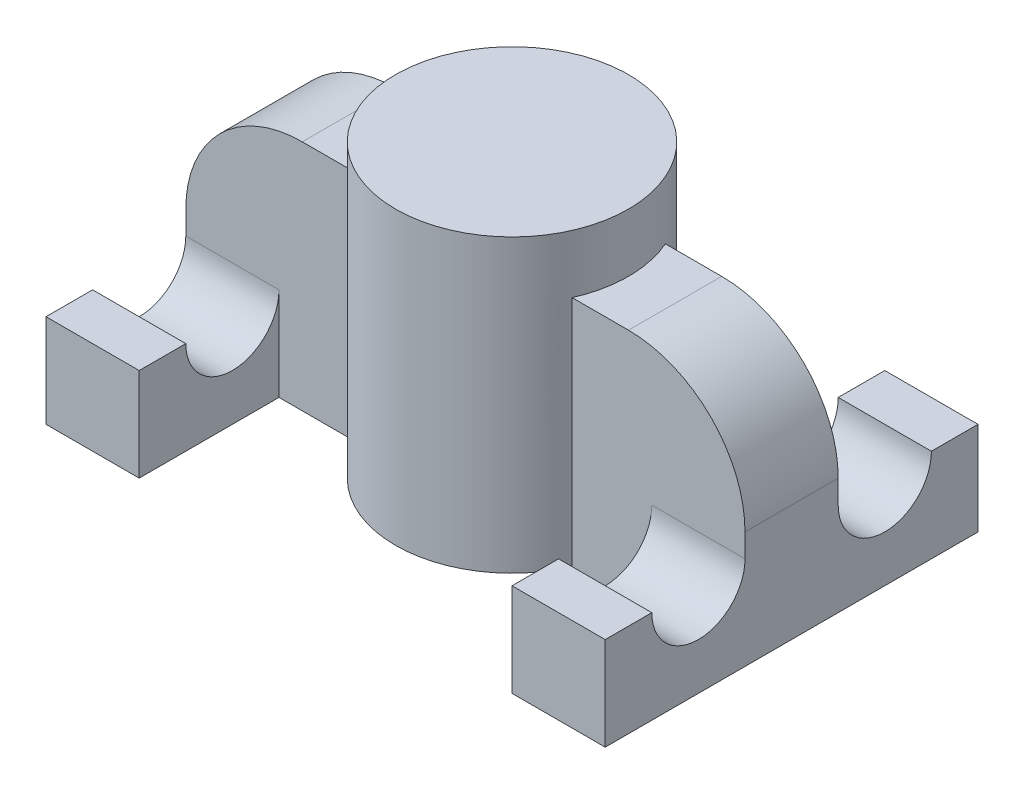
SolidWorks part; units mm, degrees
ref_plane "Front Plane" through (0, 0, 0) normal (0, 0, 1) x (1, 0, 0)
ref_plane "Top Plane" through (0, 0, 0) normal (0, 1, 0) x (1, 0, 0)
ref_plane "Right Plane" through (0, 0, 0) normal (1, 0, 0) x (0, 0, -1)
sketch "Sketch1" plane through (0, 0, 0) normal (0, 1, 0) x (1, 0, 0)
  circle A0 centre (0, 0) radius 10
  dimension "D1" = 20
extrude "Pen Cap" add sketch "Sketch1" along normal blind 25
sketch "Sketch2" plane through (0, 0, 0) normal (0, -1, 0) x (1, 0, 0)
  line L1 (-24, 4) -> (24, 4)
  line L2 (-24, 4) -> (-24, -4)
  line L3 (-24, -4) -> (24, -4)
  line L4 (24, 4) -> (24, -4)
  point P4 (0, 4)
  point P6 (-24, 0)
  dimension "D1" = 8
  dimension "D2" = 48
extrude "Hook Structure" add sketch "Sketch2" against normal blind 20
hole_wizard "Pen Centering Hole" positions "Sketch4" profile "Sketch3" legacy
sketch "Sketch4" plane through (0, 0, 0) normal (0, -1, 0) x (1, 0, 0)
  point P0 (0, 0)
sketch "Sketch3" plane through (0, 0, 0) normal (1, 0, 0) x (0, 0, -1)
  line L0 (0, 0) -> (0, 20.5)
  line L1 (0, 20.5) -> (5.5, 15)
  line L2 (5.5, 15) -> (5.5, 0)
  line L4 (5.5, 0) -> (0, 0)
  line L6 (0, 20.5) -> (-5.5, 15) construction
  line L7 (0, -4.2442) -> (0, 117.3081) construction
  dimension "Diameter" = 11
  dimension "Depth" = 15
  dimension "Drill Angle" = 90
sketch "Sketch6" plane through (24, 0, 0) normal (1, 0, 0) x (0, 0, -1)
  line L0 (-4, 0) -> (-16, 0)
  line L1 (-16, 0) -> (-16, 8)
  line L2 (-16, 8) -> (-12, 8)
  line L3 (-4, 0) -> (-4, 20) construction
  line L4 (-4, 8) -> (-4, 0)
  line L5 (0, 0) -> (0, 20) construction
  line L6 (4, 20) -> (-4, 20) construction
  line L7 (4, 8) -> (4, 0)
  line L8 (16, 8) -> (12, 8)
  line L9 (16, 0) -> (16, 8)
  line L10 (4, 0) -> (16, 0)
  arc A0 (-12, 8) -> (-4, 8) centre (-8, 8) ccw
  arc A1 (12, 8) -> (4, 8) centre (8, 8) cw
  dimension "D2" = 4
  dimension "D1" = 8
  dimension "D3" = 12
extrude "Hooks" add sketch "Sketch6" against normal blind 8
mirror "Hook Mirror" about plane through (0, 0, 0) normal (1, 0, 0) of "Hooks"
fillet "Corner Dec" radius 10 2 edges at (24, 20, 0) (-24, 20, 0)
